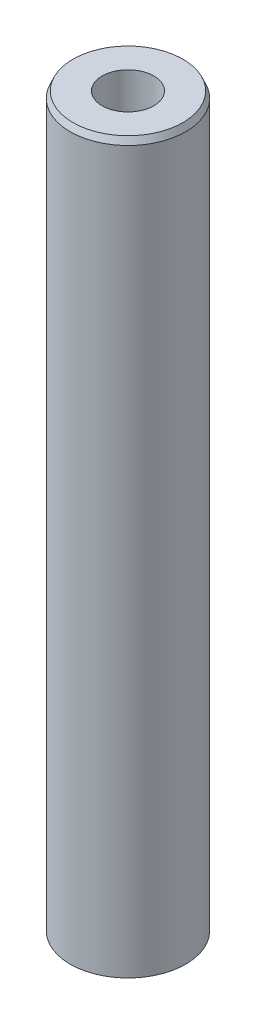
SolidWorks part; units mm, degrees
ref_plane "Front Plane" through (0, 0, 0) normal (0, 0, 1) x (1, 0, 0)
ref_plane "Top Plane" through (0, 0, 0) normal (0, 1, 0) x (1, 0, 0)
ref_plane "Right Plane" through (0, 0, 0) normal (1, 0, 0) x (0, 0, -1)
sketch "Sketch1" plane through (0, 0, 0) normal (0, 1, 0) x (1, 0, 0)
  circle A0 centre (0, 0) radius 47.5
  dimension "SHAFT_OD" = 95
extrude "Boss-Extrude1" add sketch "Sketch1" along normal blind 600
sketch "Sketch2" plane through (0, 0, 0) normal (0, 1, 0) x (1, 0, 0)
  circle A0 centre (0, 0) radius 21.2407
  dimension "BORE_D" = 42.4814
extrude "Cut-Extrude1" cut sketch "Sketch2" along normal through all
chamfer "Chamfer1" distance 5.3235 angle 23.741 2 edges at (0, 600, 47.5) (0, 0, 47.5) first distance on face at (0, 600, 47.5) first distance on face at (0, 0, 21.2407)
